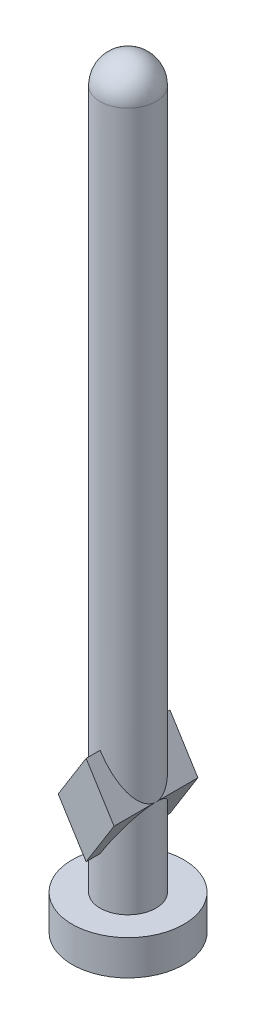
SolidWorks part; units mm, degrees
ref_plane "Front Plane" through (0, 0, 0) normal (0, 0, 1) x (1, 0, 0)
ref_plane "Top Plane" through (0, 0, 0) normal (0, 1, 0) x (1, 0, 0)
ref_plane "Right Plane" through (0, 0, 0) normal (1, 0, 0) x (0, 0, -1)
sketch "Sketch1" plane through (0, 0, 0) normal (0, 1, 0) x (1, 0, 0)
  circle A0 centre (0, 0) radius 4
extrude "Boss-Extrude1" add sketch "Sketch1" along normal blind 100
dome "Dome1" faces to dome 1 distance 4 reverse direction no elliptical dome no face at (0, 100, 4) parameters "D1"=4
sketch "Sketch2" plane through (0, 0, 0) normal (0, -1, 0) x (1, 0, 0)
  circle A0 centre (0, 0) radius 8
extrude "Boss-Extrude2" add sketch "Sketch2" along normal blind 5
sketch "Sketch3" plane through (0, 0, 0) normal (0, 0, 1) x (1, 0, 0)
  line L0 (-4, 13.1658) -> (0, 6.7594)
  line L1 (-4, 100) -> (-4, 0) construction
  line L2 (0, 6.7594) -> (4, 13.1658)
  line L3 (4, 0) -> (4, 100) construction
  line L4 (4, 13.1658) -> (0, 19.5722)
  line L5 (0, 19.5722) -> (-4, 13.1658)
  dimension "D1" = 12.8128
extrude "Boss-Extrude3" add sketch "Sketch3" along normal blind 6 and the other way blind 6
